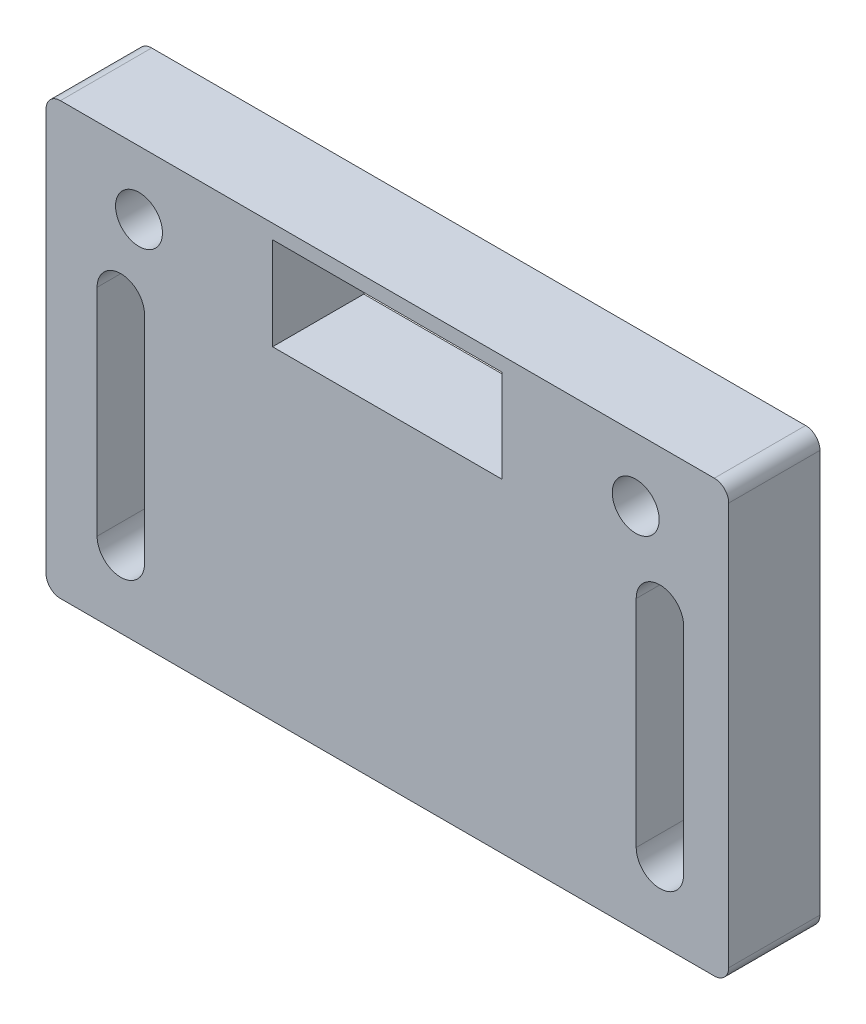
SolidWorks part; units mm, degrees
ref_plane "Front Plane" through (0, 0, 0) normal (0, 0, 1) x (1, 0, 0)
ref_plane "Top Plane" through (0, 0, 0) normal (0, 1, 0) x (1, 0, 0)
ref_plane "Right Plane" through (0, 0, 0) normal (1, 0, 0) x (0, 0, -1)
sketch "Sketch1" plane through (0, 0, 0) normal (0, 0, 1) x (1, 0, 0)
  line L0 (0, -2) -> (15.975, -2)
  line L1 (-47.5, 0) -> (47.5, 0)
  line L2 (-47.5, 0) -> (-47.5, -60)
  line L3 (-47.5, -60) -> (47.5, -60)
  line L4 (47.5, 0) -> (47.5, -60)
  line L5 (15.975, -2) -> (15.975, -14.9)
  line L6 (15.975, -14.9) -> (-15.975, -14.9)
  line L7 (-15.975, -14.9) -> (-15.975, -2)
  line L8 (-15.975, -2) -> (0, -2)
  line L9 (0, 0) -> (0, -2) construction
  point P10 (-2.3141, -2)
  dimension "D1" = 95
  dimension "D2" = 60
  dimension "D3" = 12.9
  dimension "D4" = 2
  dimension "D5" = 31.95
extrude "Boss-Extrude1" add sketch "Sketch1" along normal blind 12.7
sketch "Sketch2" plane through (0, 0, 0) normal (0, 0, -1) x (-1, 0, 0)
  line L0 (-47.5, -8.8451) -> (-34.56, -8.8451) construction
  line L1 (-47.5, -60) -> (-47.5, 0) construction
  line L2 (47.5, -8.8451) -> (34.56, -8.8451) construction
  line L3 (47.5, 0) -> (47.5, -60) construction
  line L4 (-34.56, -8.8451) -> (34.56, -8.8451) construction
  dimension "D1" = 69.12
hole_wizard "CSK for 1/4 Flat Head Machine Screw2" positions "Sketch5" profile "Sketch6" countersink size "1/4" standard "ANSI Inch" end condition through all
sketch "Sketch5" plane through (0, 0, 0) normal (0, 0, -1) x (-1, 0, 0)
  point P0 (-34.56, -8.8451)
  point P3 (34.56, -8.8451)
  point P6 (-64.56, -8.35)
sketch "Sketch6" plane through (34.56, -8.8451, 0) normal (1, 0, 0) x (0, 1, 0)
  line L0 (0, 0) -> (0, 12.7)
  line L1 (0, 12.7) -> (3.2639, 12.7)
  line L2 (3.2639, 12.7) -> (3.2639, 3.6524)
  line L3 (3.2639, 3.6524) -> (6.4389, 0)
  line L5 (6.4389, 0) -> (0, 0)
  line L6 (-3.2639, 3.6524) -> (-6.4389, 0) construction
  line L11 (0, -6.35) -> (0, 107.95) construction
  dimension "Thru Hole Dia." = 6.5278
  dimension "Thru Hole Depth" = 12.7
  dimension "Near C'Sink Dia." = 12.8778
  dimension "Near C'Sink Angle" = 82
fillet "Fillet1" radius 2 2 edges at (-47.5, 0, 6.35) (-47.5, -60, 6.35)
fillet "Fillet2" radius 2 2 edges at (47.5, -60, 6.35) (47.5, 0, 6.35)
sketch "Sketch9" plane through (0, 0, 0) normal (0, 0, -1) x (-1, 0, 0)
  line L0 (-41.2257, -19.9409) -> (-41.2257, -49.9409)
  line L1 (-34.6257, -49.9409) -> (-34.6257, -19.9409)
  line L2 (-47.5, -58) -> (-47.5, -2) construction
  line L3 (-34.6257, -40.8453) -> (33.7943, -40.8453)
  line L4 (33.7943, -49.9409) -> (33.7943, -19.9409)
  line L5 (40.3943, -49.9409) -> (40.3943, -19.9409)
  line L6 (45.5, -60) -> (-45.5, -60) construction
  arc A0 (-34.6257, -49.9409) -> (-41.2257, -49.9409) centre (-37.9257, -49.9409) cw
  arc A1 (-34.6257, -19.9409) -> (-41.2257, -19.9409) centre (-37.9257, -19.9409) ccw
  arc A2 (33.7943, -49.9409) -> (40.3943, -49.9409) centre (37.0943, -49.9409) ccw
  arc A3 (40.3943, -19.9409) -> (33.7943, -19.9409) centre (37.0943, -19.9409) ccw
  dimension "D1" = 3.3
  dimension "D5" = 3.3
  dimension "D8" = 30
  dimension "D2" = 30
  dimension "D3" = 6.2743
  dimension "D4" = 68.42
  dimension "D6" = 10.0591
  dimension "D7" = 10.0591
extrude "Cut-Extrude1" cut sketch "Sketch9" against normal through all contours L1 A1 L0 A0 | L5 A3 L4 A2 region at (37.9257, -34.9409, 0) region at (-37.0943, -34.9409, 0)
